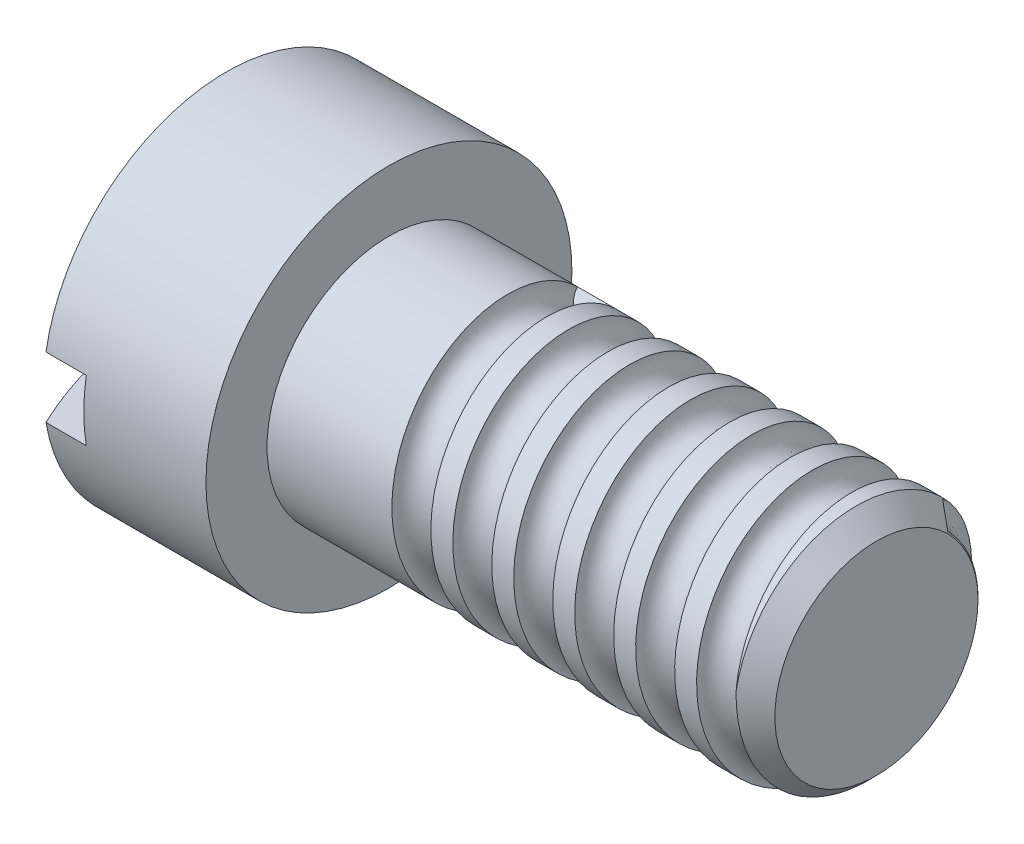
SolidWorks part; units mm, degrees
material "Alloy Steel"
ref_plane "Front Plane" through (0, 0, 0) normal (0, 0, 1) x (1, 0, 0)
ref_plane "Top Plane" through (0, 0, 0) normal (0, 1, 0) x (1, 0, 0)
ref_plane "Right Plane" through (0, 0, 0) normal (1, 0, 0) x (0, 0, -1)
sketch "Sketch2" plane through (0, 0, 0) normal (0, 0, 1) x (1, 0, 0)
  line L0 (0, 0) -> (0, 4.7625)
  line L1 (0, 4.7625) -> (-19.05, 4.7625)
  line L2 (-19.05, 4.7625) -> (-19.05, 7.1501)
  line L3 (-19.05, 7.1501) -> (-25.4, 7.1501)
  line L7 (-23.8252, 0) -> (0, 0)
  line L8 (11.8186, 0) -> (-43.1188, 0) construction
  line L11 (-27.0002, 1.1938) -> (-27.0002, 0)
  line L12 (-27.0002, 0) -> (-23.8252, 0)
  arc A0 (-25.4, 7.1501) -> (-27.0002, 1.1938) centre (-10.6712, 0) ccw
  point P12 (-22.225, 7.1501)
  dimension "D1" = 19.05
  dimension "D2" = 6.35
  dimension "D5" = 14.3002
  dimension "D6" = 9.525
  dimension "D7" = 7.9502
revolve "Revolve1" add sketch "Sketch2" angle 360 about L8
ref_plane "Plane1" through (0, 0, 10.16) normal (0, 0, 1) x (1, 0, 0)
sketch "Sketch3" plane through (0, 0, 10.16) normal (0, 0, 1) x (1, 0, 0)
  line L0 (-19.05, -7.1501) -> (-19.05, 7.1501) construction
  line L1 (-29.0337, 1.1906) -> (-23.8252, 1.1906)
  line L2 (-29.0337, 1.1906) -> (-29.0337, -1.1906)
  line L3 (-29.0337, -1.1906) -> (-23.8252, -1.1906)
  line L4 (-23.8252, 1.1906) -> (-23.8252, -1.1906)
  line L5 (7.8651, 0) -> (-7.8651, 0) construction
  point P8 (-29.0337, 0)
  dimension "D1" = 2.3813
  dimension "D2" = 4.7752
  dimension "D3" = 0
extrude "Cut-Extrude1" cut sketch "Sketch3" against normal through all
chamfer "Chamfer1" distance 0.7937 angle 45 1 edges at (0, 0, -4.7625)
sketch "Sketch13" plane through (0, 0, 0) normal (1, 0, 0) x (0, 0, -1)
  circle A0 centre (0, 0) radius 3.9688 construction
  circle A1 centre (0, 0) radius 3.9688
ref_plane "Plane2" through (0, 0, 0) normal (1, 0, 0) x (0, 0, -1)
sketch "Sketch14" plane through (0, 0, 0) normal (1, 0, 0) x (0, 0, -1)
  circle A0 centre (0, 0) radius 4.7625 construction
  circle A1 centre (0, 0) radius 4.7625
curve "Helix/Spiral1" pitch 2.3813 height 14.2875 radius 4.7625 centre (0, 0, 0) axis (-1, 0, 0) start towards (0, 0.7071, -0.7071)
ref_axis "Axis1" through (-19.05, 0, 0) along (1, 0, 0)
ref_plane "Plane3" through (0, 0, 0) normal (0, 0.7071, 0.7071) x (1, 0, 0)
sketch "Sketch15" plane through (0, 0, 0) normal (0, 0.7071, 0.7071) x (1, 0, 0)
  circle A0 centre (0, 4.7805) radius 0.762
  dimension "D1" = 1.524
sweep "Cut-Sweep1" cut profiles "Sketch15" path "Helix/Spiral1" align with end faces yes
